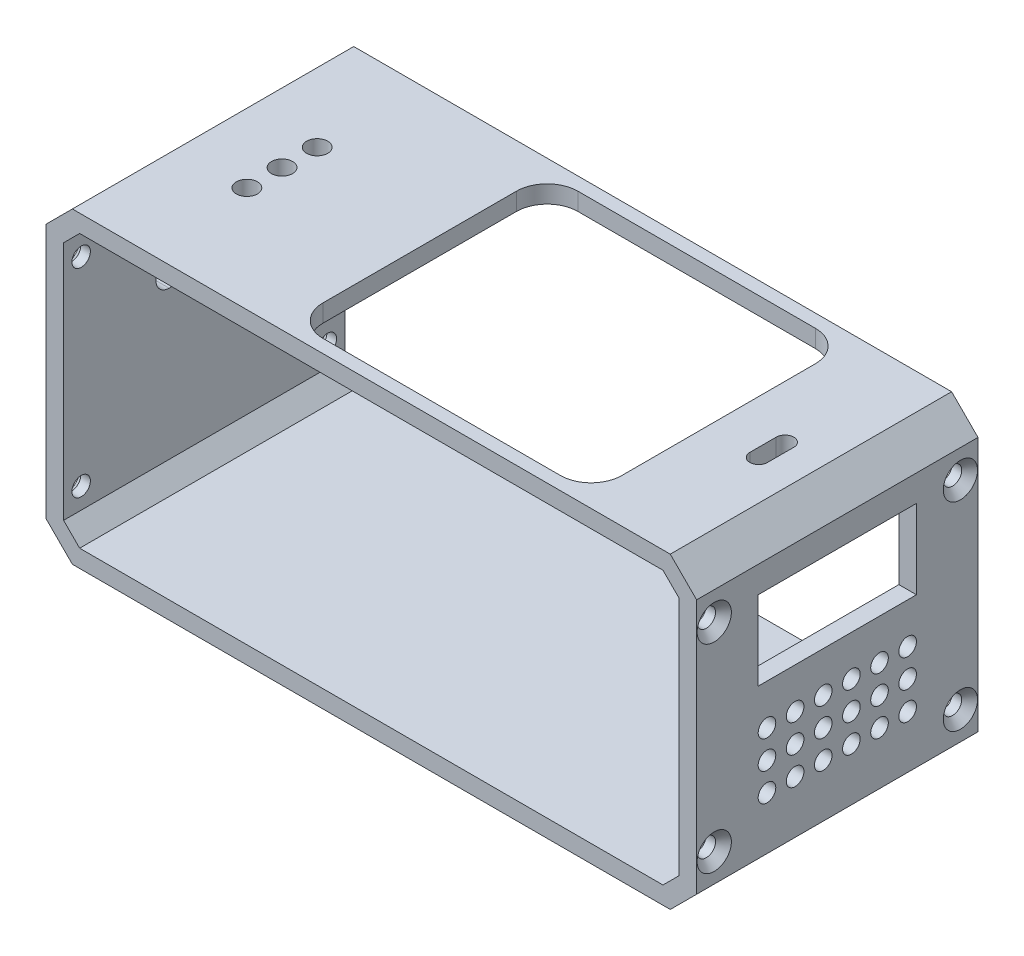
SolidWorks part; units mm, degrees
ref_plane "前视基准面" through (0, 0, 0) normal (0, 0, 1) x (1, 0, 0)
ref_plane "上视基准面" through (0, 0, 0) normal (0, 1, 0) x (1, 0, 0)
ref_plane "右视基准面" through (0, 0, 0) normal (1, 0, 0) x (0, 0, -1)
other "Configuration Table"
sketch "草图1" plane through (0, 0, 0) normal (0, 1, 0) x (1, 0, 0)
  line L0 (-32.2834, 0.435) -> (-71.9856, 0.435) construction
  line L1 (-36.9634, 16.435) -> (37.0366, 16.435)
  line L2 (-36.9634, 16.435) -> (-36.9634, -15.565)
  line L3 (-36.9634, -15.565) -> (37.0366, -15.565)
  line L4 (37.0366, 16.435) -> (37.0366, -15.565)
  line L6 (-32.2834, 11.935) -> (-32.2834, -11.065) construction
  point P6 (-36.9634, 0.435)
  point P9 (-32.2834, 0.435)
  dimension "D1" = 32
  dimension "D2" = 74
extrude "凸台-拉伸1" add sketch "草图1" along normal blind 35
chamfer "倒角1" distance 3 angle 45 4 edges at (37.0366, 0, -0.435) (-36.9634, 0, -0.435) (-36.9634, 35, -0.435) (37.0366, 35, -0.435)
sketch "草图2" plane through (0, 0, 15.565) normal (0, 0, 1) x (1, 0, 0)
  line L8 (-33.135, 2) -> (33.2082, 2)
  line L9 (35.0366, 3.8284) -> (35.0366, 31.1716)
  line L10 (33.2082, 33) -> (-33.135, 33)
  line L11 (-34.9634, 31.1716) -> (-34.9634, 3.8284)
  line L12 (-33.135, 2) -> (33.2082, 2)
  line L13 (35.0366, 3.8284) -> (35.0366, 31.1716)
  line L14 (33.2082, 33) -> (-33.135, 33)
  line L15 (-34.9634, 31.1716) -> (-34.9634, 3.8284)
  line L16 (33.2082, 2) -> (35.0366, 3.8284)
  line L17 (33.2082, 2) -> (35.0366, 3.8284)
  line L18 (35.0366, 31.1716) -> (33.2082, 33)
  line L19 (35.0366, 31.1716) -> (33.2082, 33)
  line L20 (-33.135, 33) -> (-34.9634, 31.1716)
  line L21 (-33.135, 33) -> (-34.9634, 31.1716)
  line L22 (-34.9634, 3.8284) -> (-33.135, 2)
  line L23 (-34.9634, 3.8284) -> (-33.135, 2)
  dimension "D1" = 2
extrude "切除-拉伸1" cut sketch "草图2" against normal through all
sketch "草图4" plane through (0, 35, 0) normal (0, 1, 0) x (1, 0, 0)
  line L0 (34.0366, 16.435) -> (-33.9634, 16.435) construction
  line L1 (-6.9634, 14.935) -> (20.0366, 14.935)
  line L2 (-10.4634, 11.435) -> (-10.4634, -10.565)
  line L3 (-6.9634, -14.065) -> (20.0366, -14.065)
  line L4 (23.5366, 11.435) -> (23.5366, -10.565)
  line L5 (-33.9634, -15.565) -> (34.0366, -15.565) construction
  line L7 (37.0366, 16.435) -> (37.0366, -15.565) construction
  arc A0 (20.0366, -14.065) -> (23.5366, -10.565) centre (20.0366, -10.565) ccw
  arc A1 (20.0366, 14.935) -> (23.5366, 11.435) centre (20.0366, 11.435) cw
  arc A2 (-10.4634, -10.565) -> (-6.9634, -14.065) centre (-6.9634, -10.565) ccw
  arc A3 (-6.9634, 14.935) -> (-10.4634, 11.435) centre (-6.9634, 11.435) ccw
  point P14 (23.5366, -14.065)
  point P17 (23.5366, 14.935)
  point P22 (-10.4634, 14.935)
  dimension "D5" = 3.5
  dimension "D1" = 34
  dimension "D2" = 1.5
  dimension "D3" = 1.5
  dimension "D4" = 13.5
extrude "切除-拉伸2" cut sketch "草图4" against normal up to next
sketch "草图5" plane through (0, 35, 0) normal (0, 1, 0) x (1, 0, 0)
  line L0 (-36.9634, 0.435) -> (-43.9993, 0.435) construction
  circle A0 centre (-26.1174, 0.435) radius 1.2
  circle A1 centre (-26.1174, 4.435) radius 1.2
  circle A2 centre (-26.1174, -3.565) radius 1.2
  dimension "D3" = 2.4
  dimension "D1" = 4
  dimension "D2" = 4
extrude "切除-拉伸3" cut sketch "草图5" against normal up to next
sketch "草图6" plane through (37.0366, 0, 0) normal (1, 0, 0) x (0, 0, -1)
  circle A0 centre (-13.565, 28.8) radius 1.05
  circle A1 centre (-13.565, 6.2) radius 1.05
  circle A2 centre (14.435, 6.2) radius 1.05
  circle A3 centre (14.435, 28.8) radius 1.05
  dimension "D1" = 2.1
extrude "切除-拉伸4" cut sketch "草图6" against normal through all
chamfer "倒角2" distance 0.9 angle 45 8 edges at (37.0366, 28.8, -15.485) (37.0366, 6.2, -15.485) (37.0366, 28.8, 12.515) (37.0366, 6.2, 12.515) (-36.9634, 6.2, -15.485) (-36.9634, 28.8, -15.485) (-36.9634, 6.2, 12.515) (-36.9634, 28.8, 12.515)
sketch "草图7" plane through (0, 35, 0) normal (0, 1, 0) x (1, 0, 0)
  line L0 (34.0366, 0.435) -> (47.8552, 0.435) construction
  line L2 (29.5366, 1.9891) -> (29.5366, -1.0109) construction
  line L3 (30.5366, 1.9891) -> (30.5366, -1.0109)
  line L4 (28.5366, 1.9891) -> (28.5366, -1.0109)
  line L5 (37.0366, 16.435) -> (37.0366, -15.565) construction
  arc A0 (30.5366, 1.9891) -> (28.5366, 1.9891) centre (29.5366, 1.9891) ccw
  arc A1 (28.5366, -1.0109) -> (30.5366, -1.0109) centre (29.5366, -1.0109) ccw
  point P3 (29.5366, 0.4891)
  dimension "D3" = 1
  dimension "D1" = 7.5
  dimension "D2" = 3
extrude "切除-拉伸5" cut sketch "草图7" against normal up to next
sketch "草图8" plane through (-36.9634, 0, 0) normal (-1, 0, 0) x (0, 0, 1)
  line L0 (-2.435, 11.4156) -> (-2.435, -8.1835) construction
  line L1 (-8.435, 22.2) -> (3.565, 22.2) construction
  line L2 (-8.435, 23.7) -> (3.565, 23.7)
  line L3 (-8.435, 20.7) -> (3.565, 20.7)
  line L4 (-16.435, 32) -> (-16.435, 3) construction
  line L5 (-16.435, 35) -> (15.565, 35) construction
  arc A0 (-8.435, 23.7) -> (-8.435, 20.7) centre (-8.435, 22.2) ccw
  arc A1 (3.565, 20.7) -> (3.565, 23.7) centre (3.565, 22.2) ccw
  point P3 (-2.435, 22.2)
  dimension "D4" = 1.5
  dimension "D1" = 14
  dimension "D2" = 12
  dimension "D3" = 12.8
extrude "切除-拉伸6" cut sketch "草图8" against normal up to next
sketch "草图9" plane through (-36.9634, 0, 0) normal (-1, 0, 0) x (0, 0, 1)
  line L0 (-16.435, 32) -> (-16.435, 3) construction
  line L1 (-7.435, 17) -> (-3.435, 17)
  line L2 (-7.435, 17) -> (-7.435, 15)
  line L3 (-7.435, 15) -> (-3.435, 15)
  line L4 (-3.435, 17) -> (-3.435, 15)
  line L5 (-16.435, 35) -> (15.565, 35) construction
  dimension "D1" = 9
  dimension "D2" = 2
  dimension "D3" = 18
  dimension "D4" = 4
extrude "切除-拉伸7" cut sketch "草图9" against normal up to next
fillet "圆角1" radius 1 4 edges at (-35.9634, 15, -3.435) (-35.9634, 17, -3.435) (-35.9634, 17, -7.435) (-35.9634, 15, -7.435)
sketch "草图10" plane through (-36.9634, 0, 0) normal (-1, 0, 0) x (0, 0, 1)
  line L0 (-16.435, 35) -> (15.565, 35) construction
  line L1 (-16.435, 32) -> (-16.435, 3) construction
  circle A0 centre (-8.935, 28.6) radius 1
  circle A1 centre (-5.735, 28.6) radius 1
  circle A2 centre (-2.535, 28.6) radius 1
  circle A3 centre (0.665, 28.6) radius 1
  circle A4 centre (3.865, 28.6) radius 1
  circle A5 centre (-5.735, 25.4) radius 1
  circle A6 centre (-2.535, 25.4) radius 1
  circle A7 centre (0.665, 25.4) radius 1
  circle A8 centre (3.865, 25.4) radius 1
  circle A9 centre (-8.935, 25.4) radius 1
  dimension "D3" = 2
  dimension "D1" = 6.4
  dimension "D2" = 7.5
  dimension "D4" = 5
  dimension "D5" = 2
extrude "切除-拉伸8" cut sketch "草图10" against normal up to next
sketch "草图11" plane through (37.0366, 0, 0) normal (1, 0, 0) x (0, 0, -1)
  line L0 (-15.565, 3) -> (16.435, 3) construction
  line L1 (-8.565, 29) -> (9.435, 29)
  line L3 (-8.565, 20) -> (9.435, 20)
  line L5 (-15.565, 35) -> (16.435, 35) construction
  line L18 (-8.565, 29) -> (-8.565, 20)
  line L19 (9.435, 29) -> (9.435, 20)
  point P6 (0.435, 3)
  point P7 (0.435, 29)
  dimension "D1" = 18
  dimension "D3" = 6
  dimension "D4" = 9
extrude "切除-拉伸9" cut sketch "草图11" against normal up to next
sketch "草图12" plane through (37.0366, 0, 0) normal (1, 0, 0) x (0, 0, -1)
  line L0 (16.435, 0) -> (-15.565, 0) construction
  line L1 (-15.565, 0) -> (-15.565, 3) construction
  line L2 (-8.565, 28) -> (-8.565, 12.1375) construction
  circle A0 centre (-7.565, 9) radius 1
  circle A1 centre (-4.365, 9) radius 1
  circle A2 centre (-1.165, 9) radius 1
  circle A3 centre (2.035, 9) radius 1
  circle A4 centre (5.235, 9) radius 1
  circle A5 centre (8.435, 9) radius 1
  circle A6 centre (-4.365, 12.2) radius 1
  circle A7 centre (-1.165, 12.2) radius 1
  circle A8 centre (2.035, 12.2) radius 1
  circle A9 centre (5.235, 12.2) radius 1
  circle A10 centre (8.435, 12.2) radius 1
  circle A11 centre (-4.365, 15.4) radius 1
  circle A12 centre (-1.165, 15.4) radius 1
  circle A13 centre (2.035, 15.4) radius 1
  circle A14 centre (5.235, 15.4) radius 1
  circle A15 centre (8.435, 15.4) radius 1
  circle A16 centre (-7.565, 12.2) radius 1
  circle A17 centre (-7.565, 15.4) radius 1
  dimension "D1" = 2
  dimension "D2" = 9
  dimension "D3" = 8
extrude "切除-拉伸10" cut sketch "草图12" against normal up to next
